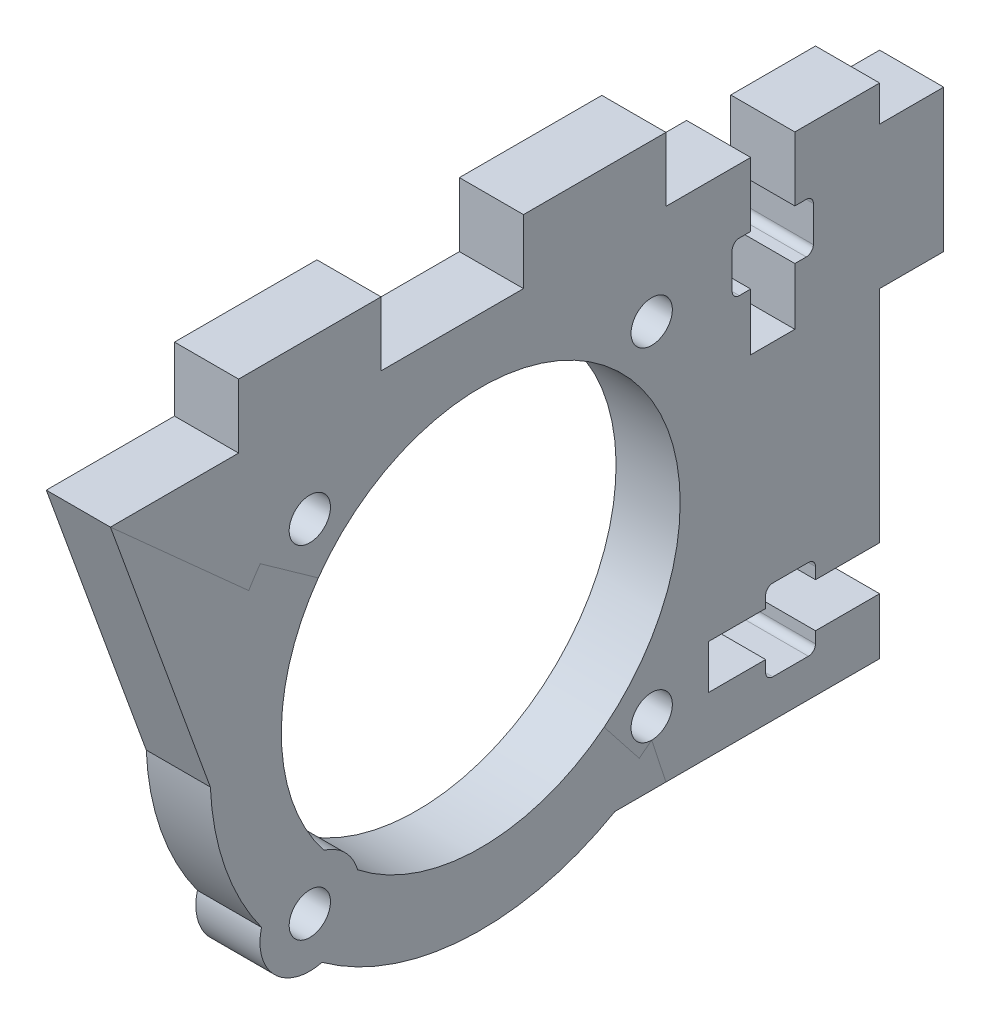
SolidWorks part; units mm, degrees
ref_plane "Front Plane" through (0, 0, 0) normal (0, 0, 1) x (1, 0, 0)
ref_plane "Top Plane" through (0, 0, 0) normal (0, 1, 0) x (1, 0, 0)
ref_plane "Right Plane" through (0, 0, 0) normal (1, 0, 0) x (0, 0, -1)
sketch "Sketch1" plane through (0, 0, 0) normal (1, 0, 0) x (0, 0, -1)
  line L0 (0, 0) -> (0, -35)
  line L1 (0, -35) -> (-54, 0)
  line L2 (-54, 0) -> (0, 0)
  dimension "D1" = 35
  dimension "D2" = 54
extrude "Boss-Extrude1" add sketch "Sketch1" along normal blind 4.5
sketch "Sketch2" plane through (4.5, 0, 0) normal (1, 0, 0) x (0, 0, -1)
  line L0 (0, -35) -> (0, 0) construction
  line L1 (-4.5, -2.5) -> (4.5, -2.5)
  line L2 (-4.5, -2.5) -> (-4.5, -12.5)
  line L3 (-4.5, -12.5) -> (4.5, -12.5)
  line L4 (4.5, -2.5) -> (4.5, -12.5)
  line L5 (-4.5, -2.5) -> (4.5, -12.5) construction
  line L6 (-4.5, -12.5) -> (4.5, -2.5) construction
  line L7 (0, 0) -> (-54, 0) construction
  point P0 (0, -7.5)
  dimension "D1" = 10
  dimension "D2" = 7.5
  dimension "D3" = 4.5
extrude "Boss-Extrude2" add sketch "Sketch2" against normal through all
sketch "Sketch3" plane through (4.5, 0, 0) normal (1, 0, 0) x (0, 0, -1)
  line L0 (0, -35) -> (-15, -35)
  line L1 (0, -25) -> (-54, 0)
  line L4 (0, -35) -> (0, -12.5) construction
  line L5 (0, -25) -> (0, -35)
  line L6 (-54, 0) -> (-15, -35)
  dimension "D1" = 15
  dimension "D2" = 10
extrude "Boss-Extrude3" add sketch "Sketch3" against normal through all
sketch "Sketch4" plane through (4.5, 0, 0) normal (1, 0, 0) x (0, 0, -1)
  line L0 (0, -29.5) -> (-12, -29.5) construction
  line L1 (0, -35) -> (0, -12.5) construction
  line L2 (0, -27.95) -> (-12, -27.95) construction
  line L3 (-12, -27.95) -> (-12, -31.05) construction
  line L4 (0, -31.05) -> (0, -27.95)
  line L5 (0, -27.95) -> (-4.5, -27.95)
  line L6 (-4.5, -27.95) -> (-4.5, -27.15)
  line L7 (-5, -26.65) -> (-7.5, -26.65)
  line L8 (-8, -27.15) -> (-8, -27.95)
  line L9 (-8, -27.95) -> (-12, -27.95)
  line L10 (-12, -27.95) -> (-12, -31.05)
  line L12 (0, -31.05) -> (-12, -31.05) construction
  line L13 (-8, -31.05) -> (-12, -31.05)
  line L14 (-8, -31.85) -> (-8, -31.05)
  line L15 (-5, -32.35) -> (-7.5, -32.35)
  line L16 (-4.5, -31.05) -> (-4.5, -31.85)
  line L17 (0, -31.05) -> (-4.5, -31.05)
  line L18 (4.5, -12.5) -> (4.5, -2.5) construction
  line L19 (0, -18.5) -> (-33.3857, -18.5) construction
  line L20 (-54, 0) -> (-15, -35) construction
  line L37 (0, -31.05) -> (-12, -31.05) construction
  arc A0 (-8, -31.85) -> (-7.5, -32.35) centre (-7.5, -31.85) ccw
  arc A1 (-5, -32.35) -> (-4.5, -31.85) centre (-5, -31.85) ccw
  arc A2 (-4.5, -27.15) -> (-5, -26.65) centre (-5, -27.15) ccw
  arc A3 (-7.5, -26.65) -> (-8, -27.15) centre (-7.5, -27.15) ccw
  point P10 (4.5, -7.5)
  point P20 (-8, -32.35)
  point P23 (-4.5, -32.35)
  point P26 (-4.5, -26.65)
  point P29 (-8, -26.65)
  dimension "D7" = 0.5
  dimension "D1" = 12
  dimension "D2" = 1.55
  dimension "D3" = 2.85
  dimension "D4" = 3.5
  dimension "D5" = 8
  dimension "D6" = 22
extrude "Cut-Extrude1" cut sketch "Sketch4" against normal through all
sketch "Sketch5" plane through (4.5, 0, 0) normal (1, 0, 0) x (0, 0, -1)
  line L0 (0, 0) -> (-54, 0) construction
  line L1 (-25, 4.5) -> (-15, 4.5)
  line L2 (-25, 4.5) -> (-25, 0)
  line L3 (0, 0) -> (-54, 0) construction
  line L4 (-15, 4.5) -> (-15, 0)
  line L5 (-25, 4.5) -> (-20, 0) construction
  line L6 (-20, 0) -> (-15, 4.5) construction
  line L7 (-30, 0) -> (-30, 4.5) construction
  line L8 (-40, 0) -> (-45, 4.5) construction
  line L9 (-35, 4.5) -> (-40, 0) construction
  line L10 (-45, 4.5) -> (-45, 0)
  line L12 (-35, 4.5) -> (-35, 0)
  line L13 (-35, 4.5) -> (-45, 4.5)
  line L14 (-20, 0) -> (-15, 4.5) construction
  line L15 (-15, 0) -> (-25, 0)
  line L16 (-35, 0) -> (-45, 0)
  point P0 (-20, 0)
  point P14 (-40, 0)
  dimension "D3" = 4.5
  dimension "D1" = 20
  dimension "D2" = 10
  dimension "D4" = 20
  dimension "D5" = 5
extrude "Boss-Extrude4" add sketch "Sketch5" against normal through all
sketch "Sketch8" [suppressed] plane through (4.5, 0, 0) normal (1, 0, 0) x (0, 0, -1)
  line L0 (-15, -30) -> (-27, -30) construction
  line L1 (-15, -35) -> (-27, -35)
  line L2 (-15, -25) -> (-27, -25)
  line L3 (-15, -35) -> (0, -35) construction
  line L4 (-15, -25) -> (-15, -35)
  arc A1 (-27, -25) -> (-27, -35) centre (-27, -30) ccw
  dimension "D5" = 5
  dimension "D1" = 0
  dimension "D2" = 12
  dimension "D3" = 0
  dimension "D4" = 10
extrude "Boss-Extrude5" [suppressed] add sketch "Sketch8" against normal up to surface (4.5 mm away) up to face at (0, -17.3125, 11.9375)
sketch "Sketch9" [suppressed] plane through (4.5, 0, 0) normal (1, 0, 0) x (0, 0, -1)
  line L0 (-27, -30) -> (-22, -30) construction
  line L1 (-27, -27) -> (-22, -27)
  line L2 (-27, -33) -> (-22, -33)
  arc A0 (-27, -27) -> (-27, -33) centre (-27, -30) ccw
  arc A1 (-22, -33) -> (-22, -27) centre (-22, -30) ccw
  point P3 (-24.5, -30)
  dimension "D1" = 3
  dimension "D2" = 5
extrude "Cut-Extrude3" [suppressed] cut sketch "Sketch9" against normal through all
sketch "Sketch10" plane through (0, 0, 0) normal (-1, 0, 0) x (0, 0, 1)
  line L0 (15, -35) -> (54, -12)
  line L1 (54, -12) -> (54, 0)
  line L3 (54, 0) -> (15, -35)
  dimension "D1" = 12
extrude "Boss-Extrude6" [suppressed] add sketch "Sketch10" against normal through all
sketch "Sketch6" plane through (4.5, 0, 0) normal (1, 0, 0) x (0, 0, -1)
  line L0 (-30, 0) -> (-30, -11) construction
  line L1 (-25, 0) -> (-35, 0) construction
  line L2 (-28.45, -11) -> (-31.55, -11) construction
  line L3 (-31.55, -11) -> (-31.55, 0) construction
  line L4 (-28.45, 0) -> (-31.55, 0)
  line L5 (-31.55, 0) -> (-31.55, -4.5)
  line L6 (-31.55, -4.5) -> (-32.35, -4.5)
  line L7 (-32.85, -5) -> (-32.85, -7.5)
  line L8 (-32.35, -8) -> (-31.55, -8)
  line L9 (-31.55, -8) -> (-31.55, -11)
  line L10 (-31.55, -11) -> (-28.45, -11)
  line L11 (-28.45, -11) -> (-28.45, 0) construction
  line L12 (-28.45, -8) -> (-28.45, -11)
  line L13 (-27.65, -8) -> (-28.45, -8)
  line L14 (-27.15, -5) -> (-27.15, -7.5)
  line L15 (-28.45, -4.5) -> (-27.65, -4.5)
  line L16 (-28.45, 0) -> (-28.45, -4.5)
  arc A0 (-32.85, -7.5) -> (-32.35, -8) centre (-32.35, -7.5) ccw
  arc A1 (-32.35, -4.5) -> (-32.85, -5) centre (-32.35, -5) ccw
  arc A2 (-27.65, -4.5) -> (-27.15, -5) centre (-27.65, -5) cw
  arc A3 (-27.15, -7.5) -> (-27.65, -8) centre (-27.65, -7.5) cw
  point P12 (-32.85, -8)
  point P15 (-32.85, -4.5)
  point P26 (-27.15, -4.5)
  point P27 (-27.15, -8)
  dimension "D2" = 1.55
  dimension "D4" = 3.5
  dimension "D6" = 0.5
  dimension "D1" = 11
  dimension "D3" = 8
  dimension "D5" = 2.85
extrude "Cut-Extrude2" [suppressed] cut sketch "Sketch6" against normal through all
sketch "Sketch11" plane through (0, 0, 0) normal (-1, 0, 0) x (0, 0, 1)
  line L0 (7.5, 0) -> (7.5, -12) construction
  line L1 (0, 0) -> (15, 0) construction
  line L2 (5.95, -12) -> (9.05, -12)
  line L3 (9.05, -12) -> (9.05, -8)
  line L4 (9.05, -8) -> (9.85, -8)
  line L5 (10.35, -7.5) -> (10.35, -5)
  line L6 (9.85, -4.5) -> (9.05, -4.5)
  line L7 (9.05, -4.5) -> (9.05, 0)
  line L8 (9.05, 0) -> (5.95, 0)
  line L9 (9.05, -8) -> (9.05, -4.5) construction
  line L10 (0, 0) -> (15, 0) construction
  line L11 (5.95, -8) -> (5.95, -4.5) construction
  line L12 (5.95, -4.5) -> (5.95, 0)
  line L13 (5.15, -4.5) -> (5.95, -4.5)
  line L14 (4.65, -7.5) -> (4.65, -5)
  line L15 (5.95, -8) -> (5.15, -8)
  line L16 (5.95, -12) -> (5.95, -8)
  arc A0 (10.35, -5) -> (9.85, -4.5) centre (9.85, -5) ccw
  arc A1 (5.15, -4.5) -> (4.65, -5) centre (5.15, -5) ccw
  arc A2 (9.85, -8) -> (10.35, -7.5) centre (9.85, -7.5) ccw
  arc A3 (4.65, -7.5) -> (5.15, -8) centre (5.15, -7.5) ccw
  point P11 (7.5, 0)
  point P22 (10.35, -4.5)
  point P25 (4.65, -4.5)
  point P28 (10.35, -8)
  point P31 (4.65, -8)
  dimension "D7" = 0.5
  dimension "D1" = 12
  dimension "D3" = 2.85
  dimension "D8" = 0.5
  dimension "D2" = 3.5
  dimension "D4" = 8
  dimension "D5" = 1.55
  dimension "D6" = 0
extrude "Cut-Extrude4" cut sketch "Sketch11" against normal through all
sketch "Sketch12" plane through (0, 0, 0) normal (-1, 0, 0) x (0, 0, 1)
  line L0 (28, -18.5) -> (16, -6.5) construction
  line L1 (28, -18.5) -> (28, -4.5) construction
  line L2 (28, -18.5) -> (40, -6.5) construction
  line L3 (28, -18.5) -> (14, -18.5) construction
  line L4 (28, -18.5) -> (16, -30.5) construction
  line L5 (28, -18.5) -> (16, -6.5) construction
  line L6 (0, -27.95) -> (0, -12.5) construction
  line L7 (25, 0) -> (35, 0) construction
  circle A0 centre (28, -18.5) radius 14
  circle A1 centre (16, -6.5) radius 1.45
  circle A2 centre (40, -6.5) radius 1.45
  circle A3 centre (16, -30.5) radius 1.45
  dimension "D1" = 28
  dimension "D2" = 2.9
  dimension "D3" = 12
  dimension "D4" = 45
  dimension "D5" = 28
  dimension "D6" = 18.5
extrude "FanCutout" cut sketch "Sketch12" against normal through all
sketch "Sketch13" plane through (0, 0, 0) normal (-1, 0, 0) x (0, 0, 1)
  line L0 (39.4071, -10.3834) -> (43.481, -7.4847)
  line L1 (19.3358, -29.4969) -> (16.2414, -33.4243)
  line L6 (28, -18.5) -> (54, 0) construction
  line L7 (28, -18.5) -> (15, -35) construction
  arc A0 (19.3358, -29.4969) -> (39.4071, -10.3834) centre (28, -18.5) ccw
  arc A1 (16.2414, -33.4243) -> (43.481, -7.4847) centre (28, -18.5) ccw
  arc A3 (40.4722, -12.1404) -> (20.333, -30.214) centre (28, -18.5) ccw construction
  dimension "D1" = 5
extrude "Boss-Extrude7" add sketch "Sketch13" against normal through all
sketch "Sketch14" plane through (0, 0, 0) normal (-1, 0, 0) x (0, 0, 1)
  line L0 (28, -4.5) -> (28, -32.5) construction
  line L1 (28, -18.5) -> (40, -30.5) construction
  circle A0 centre (28, -18.5) radius 14 construction
  circle A1 centre (40, -30.5) radius 3.5
  dimension "D2" = 7
  dimension "D1" = 45
  dimension "D3" = 12
extrude "Boss-Extrude8" add sketch "Sketch14" against normal through all
sketch "Sketch15" plane through (0, 0, 0) normal (-1, 0, 0) x (0, 0, 1)
  line L0 (42.4749, -32.9749) -> (28, -18.5) construction
  arc A0 (39.1388, -33.8924) -> (43.3924, -29.6388) centre (40, -30.5) ccw construction
  circle A1 centre (40, -30.5) radius 1.45
  dimension "D1" = 2.9
extrude "Cut-Extrude6" cut sketch "Sketch15" against normal through all
sketch "Sketch16" [suppressed] plane through (4.5, 0, 0) normal (1, 0, 0) x (0, 0, -1)
  line L0 (0, -34.5) -> (-39, -34.5) construction
  line L1 (0, -27.95) -> (0, -12.5) construction
  line L2 (-15, -34.5) -> (-39, -34.5) construction
  line L3 (-15, -38.5) -> (-39, -38.5)
  line L4 (-15, -30.5) -> (-39, -30.5)
  arc A0 (-15, -38.5) -> (-15, -30.5) centre (-15, -34.5) ccw
  arc A1 (-39, -30.5) -> (-39, -38.5) centre (-39, -34.5) ccw
  point P5 (-27, -34.5)
  point P12 (0, -20.225)
  dimension "D1" = 4
  dimension "D2" = 34.5
  dimension "D3" = 39
  dimension "D4" = 15
extrude "Boss-Extrude9" [suppressed] add sketch "Sketch16" against normal through all
sketch "Sketch17" [suppressed] plane through (4.5, 0, 0) normal (1, 0, 0) x (0, 0, -1)
  line L0 (-43, -34.5) -> (0, -34.5) construction
  line L1 (0, -27.75) -> (0, -12.5) construction
  line L2 (-26.5, -34.5) -> (-26.5, -20.0064) construction
  arc A0 (-42.1823, -32.0766) -> (-39, -38.5) centre (-39, -34.5) ccw construction
  circle A1 centre (-39, -34.5) radius 1.55
  circle A2 centre (-14, -34.5) radius 1.55
  dimension "D1" = 2.9
  dimension "D2" = 12.5
extrude "Cut-Extrude7" [suppressed] cut sketch "Sketch17" against normal through all
sketch "Sketch18" [suppressed] plane through (4.5, 0, 0) normal (1, 0, 0) x (0, 0, -1)
  line L0 (-15, -38.5) -> (0, -35)
  line L1 (0, -35) -> (-11.0314, -35)
  line L2 (-11.0314, -35) -> (-15, -38.5)
extrude "Boss-Extrude10" [suppressed] add sketch "Sketch18" against normal through all
sketch "Sketch20" [suppressed] plane through (4.5, 0, 0) normal (1, 0, 0) x (0, 0, -1)
  line L0 (0, -35) -> (0, -31.05) construction
  line L1 (-9, -38) -> (-37.9081, -38)
  line L2 (-40.7232, -36.0371) -> (-54, 0)
  line L3 (-54, 0) -> (-15, -35)
  line L4 (-15, -35) -> (-6, -35)
  line L5 (-9, -38) -> (-6, -35)
  line L6 (-40.7232, -36.0371) -> (-40, -38) construction
  line L7 (-40, -38) -> (-37.9081, -38) construction
  arc A1 (-37.9081, -38) -> (-40.7232, -36.0371) centre (-37.9081, -35) cw
  point P0 (0, -33.025)
  point P14 (-40, -38)
  dimension "D3" = 6
  dimension "D4" = 3
  dimension "D1" = 40
  dimension "D2" = 3
  dimension "D5" = 135
extrude "Boss-Extrude11" [suppressed] add sketch "Sketch20" against normal through all
sketch "Sketch21" [suppressed] plane through (4.5, 0, 0) normal (1, 0, 0) x (0, 0, -1)
  line L0 (0, -34.5) -> (-41.2895, -34.5) construction
  line L1 (0, -35) -> (0, -31.05) construction
  line L2 (-54, 0) -> (-40.7232, -36.0371) construction
  line L3 (0, -27.95) -> (0, -12.5) construction
  circle A0 centre (-36, -34.5) radius 1.45
  circle A1 centre (-11, -34.5) radius 1.45
  dimension "D2" = 2.9
  dimension "D3" = 2.9
  dimension "D1" = 25
  dimension "D4" = 34.5
  dimension "D5" = 11
extrude "Cut-Extrude8" [suppressed] cut sketch "Sketch21" against normal through all
sketch "Sketch22" [suppressed] plane through (4.5, 0, 0) normal (1, 0, 0) x (0, 0, -1)
  line L0 (0, -27.95) -> (0, -12.5) construction
  line L1 (-25, 0) -> (-35, 0) construction
  circle A0 centre (-28, -18) radius 13.25
  dimension "D2" = 18
  dimension "D3" = 26.5
  dimension "D1" = 28
extrude "Cut-Extrude9" [suppressed] cut sketch "Sketch22" against normal through all
sketch "Sketch24" plane through (0, 0, 0) normal (-1, 0, 0) x (0, 0, 1)
  line L0 (15, -35) -> (20, -35)
  line L1 (20, -35) -> (16, -31.95)
  line L2 (16, -31.95) -> (15, -35)
  circle A0 centre (16, -30.5) radius 1.45 construction
  dimension "D1" = 5
extrude "Boss-Extrude13" add sketch "Sketch24" against normal through all
sketch "Sketch25" plane through (0, 0, 0) normal (-1, 0, 0) x (0, 0, 1)
  line L0 (54, 0) -> (46.9826, -19.3121)
  line L1 (46.9826, -19.3121) -> (44.2874, -8.7164)
  line L2 (44.2874, -8.7164) -> (54, 0)
  arc A0 (43.3924, -29.6388) -> (44.2874, -8.7164) centre (28, -18.5) ccw construction
extrude "Boss-Extrude15" add sketch "Sketch25" against normal through all
equation "\"X-ROD-SPACING\"=45"
equation "\"Y-ROD-SPACING\"=75"
equation "\"Z-ROD-SPACING\"=17.5"
equation "\"Y-BED-OFFSET\"=2"
equation "\"Y-BED-ROD-INSET\"=3.5"
equation "\"Y-BED-SCREW-SPACING\"=209"
equation "\"Y-BED-SCREW-CUTOUT-SLOT-HEIGHT\"=2"
equation "\"T-SLOT-NUT-FILLET-RADIUS\"=0.5"
equation "\"T-SLOT-SCREW-SHAFT-RADIUS\"=1.55"
equation "\"T-SLOT-SCREW-SHAFT-CUTOUT-LENGTH\"=11"
equation "\"T-SLOT-NUT-DEPTH\"=3.5"
equation "\"T-SLOT-NUT-WIDTH\"=2.85"
equation "\"T-SLOT-NUT-END-DISTANCE\"=8"
equation "\"ACRYLIC-THICKNESS\"=10"
equation "\"ACRYLIC-THICKNESS2\"=4.5"
equation "\"ACRYLIC-TAB-CUTOUT-SIZE\"=\"ACRYLIC-THICKNESS\"+\"ACRYLIC-TAB-TOLERANCE\"*2"
equation "\"ACRYLIC-TAB-WIDTH\"=\"ACRYLIC-THICKNESS\""
equation "\"ACRYLIC-M3-HOLE\"=2.9"
equation "\"SMOOTHROD-CAP-SCREW-DISTANCE\"=20"
equation "\"FRAME-WIDTH-INNER\"=370"
equation "\"NEMA17-HOLE-SPACING\"=31"
equation "\"NEMA17-CENTRAL-CUTOUT\"=22.5"
equation "\"Z-BRACKET-REACH\"=55"
equation "\"Z-ROD-INSET\"=13.5"
equation "\"TOP-BRACKET-SPACING\"=40"
equation "\"SMOOTHROD-X-LENGTH\"=350"
equation "\"SMOOTHROD-Y-LENGTH\"=350"
equation "\"SMOOTHROD-Z-LENGTH\"=350"
equation "\"SMOOTHROD-TIGHTENING-HEADROOM\"=.25"
equation "\"LEADSCREW-Z-LENGTH\"=300"
equation "\"SCREW-LENGTH-FRAME\"=\"ACRYLIC-THICKNESS\" + 10"
equation "\"SCREW-LENGTH-MOTOR\"=\"ACRYLIC-THICKNESS\" + 5"
equation "\"SCREW-LENGTH-EXTRUDER\"=28"
equation "\"SCREW-HEAD-RADIUS\"=6"
equation "\"PRINTED-X-SMOOTHROD-DIAMETER\"=9.0"
equation "\"PRINTED-X-SMOOTHROD-CUTOUT\"=10"
equation "\"PRINTED-X-BASE-HEIGHT\"=10"
equation "\"PRINTED-LM8UU-CUTOUT-SIZE\"=15.5"
equation "\"PRINTED-LM8UU-CUTOUT-LENGTH\"=24.5"
equation "\"PRINTED-X-IDLER-HEIGHT\"=16"
equation "\"PSU-MOUNTING-WIDTH\"=95"
equation "\"PSU-MOUNTING-HEIGHT\"=177"
equation "\"Y-BELT-TO-ROD-DISTANCE\"=20"
equation "\"SPOOL-HOLDER-ROD-SPACING\"=150"
equation "\"ACRYLIC-X-CARRIAGE-WIDTH\"=55"
equation "\"ACRYLIC-X-CARRIAGE-HEIGHT\"=75"
equation "\"ACRYLIC-X-CARRIAGE-SCREW-SPACING-X\"=15"
equation "\"ACRYLIC-X-CARRIAGE-SCREW-SPACING-Y\"=33"
equation "\"ACRYLIC-X-CARRIAGE-CENTER-TAB-SPACING\"=14"
equation "\"ACRYLIC-X-CARRIAGE-EXTRUDER-SHELF-DEPTH\"=\"ACRYLIC-X-CARRIAGE-EXTRUDER-OFFSET\" + 28"
equation "\"D2@Sketch1\"=\"ACRYLIC-X-CARRIAGE-EXTRUDER-SHELF-DEPTH\""
equation "\"D1@Boss-Extrude1\"=\"ACRYLIC-THICKNESS2\""
equation "\"D1@Sketch2\"=\"ACRYLIC-TAB-WIDTH\""
equation "\"D3@Sketch2\"=\"ACRYLIC-THICKNESS2\""
equation "\"ACRYLIC-X-CARRIAGE-LM8UU-CUTOUT-WIDTH\"=24.25"
equation "\"ACRYLIC-X-CARRIAGE-EXTRUDER-BRACE-SPACING\"=23"
equation "\"ACRYLIC-X-CARRIAGE-EXTRUDER-BRACE-HEIGHT\"=35"
equation "\"D1@Sketch1\"=\"ACRYLIC-X-CARRIAGE-EXTRUDER-BRACE-HEIGHT\""
equation "\"D1@Sketch4\"=\"T-SLOT-SCREW-SHAFT-CUTOUT-LENGTH\"+1"
equation "\"D2@Sketch4\"=\"T-SLOT-SCREW-SHAFT-RADIUS\""
equation "\"D3@Sketch4\"=\"T-SLOT-NUT-WIDTH\""
equation "\"D4@Sketch4\"=\"T-SLOT-NUT-DEPTH\""
equation "\"D5@Sketch4\"=\"T-SLOT-NUT-END-DISTANCE\""
equation "\"D7@Sketch4\"=\"T-SLOT-NUT-FILLET-RADIUS\""
equation "\"ACRYLIC-X-CARRIAGE-EXTRUDER-BRACE-SCREW-SPACING\"=22"
equation "\"D6@Sketch4\"=\"ACRYLIC-X-CARRIAGE-EXTRUDER-BRACE-SCREW-SPACING\""
equation "\"ACRYLIC-X-CARRIAGE-EXTRUDER-BRACE-TAB-OFFSET\"=20"
equation "\"D1@Sketch5\"=\"ACRYLIC-X-CARRIAGE-EXTRUDER-BRACE-TAB-OFFSET\""
equation "\"D2@Sketch5\"=\"ACRYLIC-TAB-WIDTH\""
equation "\"D3@Sketch5\"=\"ACRYLIC-THICKNESS2\""
equation "\"ACRYLIC-X-CARRIAGE-EXTRUDER-OFFSET\"=26"
equation "\"ACRYLIC-X-CARRIAGE-EXTRUDER-ANGLE\"=90"
equation "\"D1@Sketch6\"=\"T-SLOT-SCREW-SHAFT-CUTOUT-LENGTH\""
equation "\"D2@Sketch6\"=\"T-SLOT-SCREW-SHAFT-RADIUS\""
equation "\"D3@Sketch6\"=\"T-SLOT-NUT-END-DISTANCE\""
equation "\"D4@Sketch6\"=\"T-SLOT-NUT-DEPTH\""
equation "\"D5@Sketch6\"=\"T-SLOT-NUT-WIDTH\""
equation "\"D6@Sketch6\"=\"T-SLOT-NUT-FILLET-RADIUS\""
equation "\"D1@Sketch11\"=\"T-SLOT-SCREW-SHAFT-CUTOUT-LENGTH\"+1"
equation "\"D2@Sketch11\"=\"T-SLOT-NUT-DEPTH\""
equation "\"D3@Sketch11\"=\"T-SLOT-NUT-WIDTH\""
equation "\"D4@Sketch11\"=\"T-SLOT-NUT-END-DISTANCE\""
equation "\"D5@Sketch11\"=\"T-SLOT-SCREW-SHAFT-RADIUS\""
equation "\"D7@Sketch11\"=\"T-SLOT-NUT-FILLET-RADIUS\""
equation "\"D8@Sketch11\"=\"T-SLOT-NUT-FILLET-RADIUS\""
equation "\"D2@Sketch12\"=\"ACRYLIC-M3-HOLE\""
equation "\"D1@Sketch15\"=\"ACRYLIC-M3-HOLE\""
equation "\"D1@Sketch17\"=\"ACRYLIC-M3-HOLE\""
equation "\"D2@Sketch21\"=\"ACRYLIC-M3-HOLE\""
equation "\"D3@Sketch21\"=\"ACRYLIC-M3-HOLE\""
